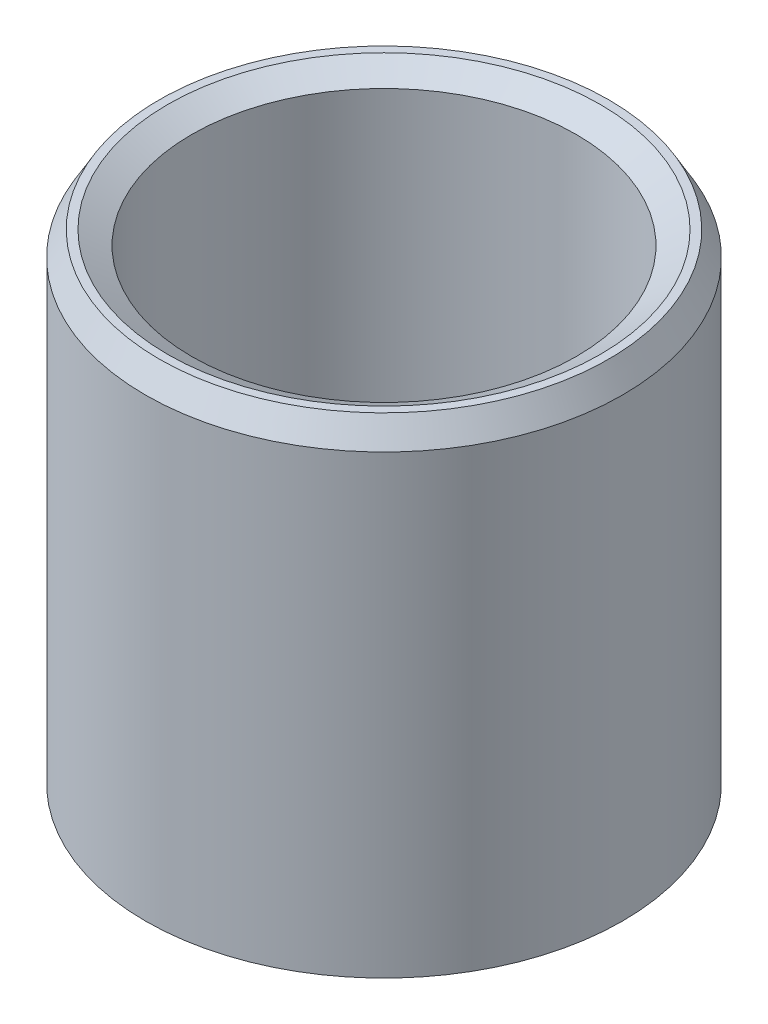
SolidWorks part; units mm, degrees
ref_plane "Front Plane" through (0, 0, 0) normal (0, 0, 1) x (1, 0, 0)
ref_plane "Top Plane" through (0, 0, 0) normal (0, 1, 0) x (1, 0, 0)
ref_plane "Right Plane" through (0, 0, 0) normal (1, 0, 0) x (0, 0, -1)
sketch "Sketch1" plane through (0, 0, 0) normal (0, 1, 0) x (1, 0, 0)
  circle A0 centre (0, 0) radius 35
  dimension "SLEEVE_OD" = 70
extrude "Boss-Extrude1" add sketch "Sketch1" along normal blind 72.4037
sketch "Sketch2" plane through (0, 0, 0) normal (0, 1, 0) x (1, 0, 0)
  circle A0 centre (0, 0) radius 28.2113
  dimension "BORE_D" = 56.4226
extrude "Cut-Extrude1" cut sketch "Sketch2" along normal through all
chamfer "Chamfer1" distance 3.5333 angle 30 4 edges at (0, 72.4037, 28.2113) (0, 0, 28.2113) (0, 0, 35) (0, 72.4037, 35) first distance on face at (0, 72.4037, 28.2113) first distance on face at (0, 0, 28.2113) first distance on face at (0, 72.4037, 35)
